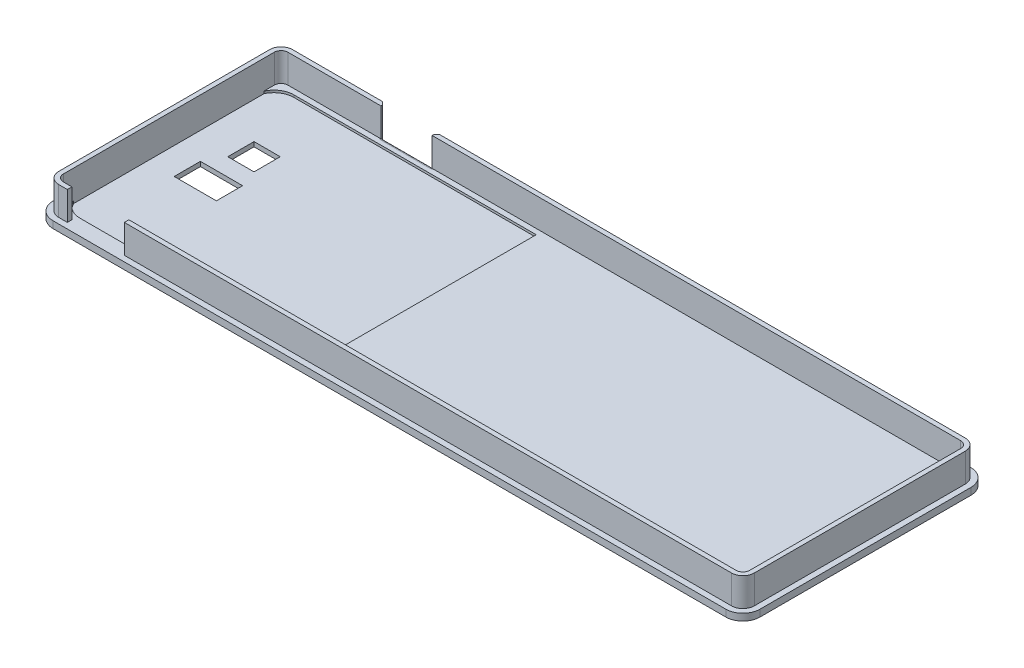
SolidWorks part; units mm, degrees
ref_plane "Спереди" through (0, 0, 0) normal (0, 0, 1) x (1, 0, 0)
ref_plane "Сверху" through (0, 0, 0) normal (0, 1, 0) x (1, 0, 0)
ref_plane "Справа" through (0, 0, 0) normal (1, 0, 0) x (0, 0, -1)
sketch "Эскиз1" plane through (0, 0, 0) normal (0, 1, 0) x (1, 0, 0)
  line L1 (105.9268, 23) -> (-18.0732, 23)
  line L2 (105.9268, 23) -> (105.9268, -20)
  line L3 (105.9268, -20) -> (-18.0732, -20)
  line L4 (-18.0732, 23) -> (-18.0732, -20)
  line L5 (105.9268, 23) -> (-18.0732, -20) construction
  line L6 (105.9268, -20) -> (-18.0732, 23) construction
  line L7 (-16.0732, 16.75) -> (-16.0732, -13.75) construction
  line L9 (103.9268, -18) -> (103.9268, 21) construction
  point P0 (0, 0)
  dimension "D1" = 43
  dimension "D2" = 2
  dimension "D3" = 2
extrude "Бобышка-Вытянуть1" add sketch "Эскиз1" along normal blind 1.2
sketch "Эскиз3" plane through (0, 0, 0) normal (0, -1, 0) x (1, 0, 0)
  line L12 (-11.5732, 2.25) -> (-11.5732, -2.35)
  line L13 (-11.5732, -2.35) -> (-4.1732, -2.35)
  line L14 (-4.1732, -2.35) -> (-4.1732, 2.25)
  line L15 (-4.1732, 2.25) -> (-11.5732, 2.25)
  line L16 (-11.5732, 2.25) -> (-11.5732, -2.35)
  line L17 (-11.5732, -2.35) -> (-4.1732, -2.35)
  line L18 (-4.1732, -2.35) -> (-4.1732, 2.25)
  line L19 (-4.1732, 2.25) -> (-11.5732, 2.25)
  line L24 (-9.8732, -5.45) -> (-9.8732, -10.05)
  line L25 (-9.8732, -10.05) -> (-5.2732, -10.05)
  line L26 (-5.2732, -10.05) -> (-5.2732, -5.45)
  line L27 (-5.2732, -5.45) -> (-9.8732, -5.45)
  line L28 (-9.8732, -5.45) -> (-9.8732, -10.05)
  line L29 (-9.8732, -10.05) -> (-5.2732, -10.05)
  line L30 (-5.2732, -10.05) -> (-5.2732, -5.45)
  line L31 (-5.2732, -5.45) -> (-9.8732, -5.45)
  dimension "D1" = 0.8
  dimension "D2" = 0.8
extrude "Вырез-Вытянуть1" cut sketch "Эскиз3" against normal up to next
sketch "Эскиз4" plane through (0, 1.2, 0) normal (0, 1, 0) x (1, 0, 0)
  line L0 (4.11, 20.25) -> (7.3436, 20.25)
  line L16 (29.4268, 20.25) -> (7.3436, 20.25)
  line L17 (7.3436, 20.25) -> (7.3436, 15.1)
  line L18 (7.3436, 15.1) -> (4.11, 15.1)
  line L19 (4.11, 15.1) -> (4.11, 20.25)
  line L20 (4.11, 20.25) -> (-13.0732, 20.25)
  line L21 (-16.5732, 16.75) -> (-16.5732, -13.75)
  line L22 (-13.0732, -17.25) -> (25.9268, -17.25)
  line L23 (29.4268, -13.75) -> (29.4268, 20.25)
  line L24 (29.4268, 20.25) -> (7.3436, 20.25)
  line L28 (4.11, 20.25) -> (-13.0732, 20.25)
  line L29 (-16.5732, 16.75) -> (-16.5732, -13.75)
  line L30 (-13.0732, -17.25) -> (25.9268, -17.25)
  line L31 (29.4268, -13.75) -> (29.4268, 20.25)
  arc A6 (-13.0732, 20.25) -> (-16.5732, 16.75) centre (-13.0732, 16.75) ccw
  arc A7 (-16.5732, -13.75) -> (-13.0732, -17.25) centre (-13.0732, -13.75) ccw
  arc A8 (25.9268, -17.25) -> (29.4268, -13.75) centre (25.9268, -13.75) ccw
  arc A9 (-13.0732, 20.25) -> (-16.5732, 16.75) centre (-13.0732, 16.75) ccw
  arc A10 (-16.5732, -13.75) -> (-13.0732, -17.25) centre (-13.0732, -13.75) ccw
  arc A11 (25.9268, -17.25) -> (29.4268, -13.75) centre (25.9268, -13.75) ccw
  dimension "D1" = 0.5
extrude "Вырез-Вытянуть2" cut sketch "Эскиз4" against normal blind 0.4
fillet "Скругление1" radius 3 4 edges at (105.9268, 0.6, -23) (105.9268, 0.6, 20) (-18.0732, 0.6, -23) (-18.0732, 0.6, 20)
sketch "Эскиз5" plane through (0, 1.2, 0) normal (0, 1, 0) x (1, 0, 0)
  line L4 (-15.0732, -18.2) -> (102.9268, -18.2)
  line L5 (104.1268, -17) -> (104.1268, 20)
  line L6 (102.9268, 21.2) -> (-15.0732, 21.2)
  line L7 (-16.2732, 20) -> (-16.2732, -17)
  line L8 (104.9268, -17) -> (104.9268, 20)
  line L9 (102.9268, 22) -> (-15.0732, 22)
  line L10 (-17.0732, 20) -> (-17.0732, -17)
  line L11 (-15.0732, -19) -> (102.9268, -19)
  line L12 (104.9268, -17) -> (104.9268, 20)
  line L13 (102.9268, 22) -> (-15.0732, 22)
  line L14 (-17.0732, 20) -> (-17.0732, -17)
  line L15 (-15.0732, -19) -> (102.9268, -19)
  arc A4 (102.9268, -18.2) -> (104.1268, -17) centre (102.9268, -17) ccw
  arc A5 (104.1268, 20) -> (102.9268, 21.2) centre (102.9268, 20) ccw
  arc A6 (-15.0732, 21.2) -> (-16.2732, 20) centre (-15.0732, 20) ccw
  arc A7 (-16.2732, -17) -> (-15.0732, -18.2) centre (-15.0732, -17) ccw
  arc A8 (104.9268, 20) -> (102.9268, 22) centre (102.9268, 20) ccw
  arc A9 (-15.0732, 22) -> (-17.0732, 20) centre (-15.0732, 20) ccw
  arc A10 (-17.0732, -17) -> (-15.0732, -19) centre (-15.0732, -17) ccw
  arc A11 (102.9268, -19) -> (104.9268, -17) centre (102.9268, -17) ccw
  arc A12 (104.9268, 20) -> (102.9268, 22) centre (102.9268, 20) ccw
  arc A13 (-15.0732, 22) -> (-17.0732, 20) centre (-15.0732, 20) ccw
  arc A14 (-17.0732, -17) -> (-15.0732, -19) centre (-15.0732, -17) ccw
  arc A15 (102.9268, -19) -> (104.9268, -17) centre (102.9268, -17) ccw
  point P16 (0, 0)
  arc M13 (-13.0732, -17.25) -> (-16.5732, -13.75) centre (-13.0732, -13.75) cw
  line M14 (-16.5732, -13.75) -> (-16.5732, 16.75)
  arc M15 (-16.5732, 16.75) -> (-13.0732, 20.25) centre (-13.0732, 16.75) cw
  dimension "D3" = 0.8
  dimension "D1" = 1
  dimension "D2" = 0.8
extrude "Бобышка-Вытянуть5" add sketch "Эскиз5" along normal blind 5 contours L15 A15 L12 A12 L13 A13 L14 A14 A7 L7 A6 L6 A5 L5 A4 L4 M13 M14 M15
ref_plane "Плоскость2" through (0, 0, 15.1677) normal (0, 0, -1) x (-1, 0, 0)
sketch "Эскиз7" plane through (0, 0, 15.1677) normal (0, 0, -1) x (-1, 0, 0)
  line L0 (17.0732, 6.2) -> (17.0732, 1.2) construction
  line L1 (16.2732, 6.2) -> (17.0732, 6.2)
  line L2 (16.2732, 6.2) -> (16.2732, 0.8)
  line L3 (16.2732, 0.8) -> (17.0732, 0.8)
  line L4 (17.0732, 6.2) -> (17.0732, 0.8)
  line L5 (16.2732, 6.2) -> (16.2732, 1.2) construction
  line L6 (16.2732, 6.2) -> (15.0732, 6.2) construction
  line L7 (4.1732, 0.8) -> (11.5732, 0.8) construction
extrude "Бобышка-Вытянуть6" add sketch "Эскиз7" along normal up to vertex
sketch "Эскиз8" plane through (0, 6.2, 0) normal (0, 1, 0) x (1, 0, 0)
  line L0 (10.2268, 21.2) -> (10.2268, 22)
  line L1 (102.9268, 21.2) -> (-15.0732, 21.2) construction
  line L2 (102.9268, 22) -> (-15.0732, 22) construction
  line L3 (1.2268, 21.2) -> (1.2268, 22)
  line L4 (5.7268, 21.2) -> (5.7268, 22) construction
  line L5 (-17.0732, 20) -> (-17.0732, -17) construction
  point P10 (10.2268, 21.6)
  point P11 (1.2268, 21.6)
  line M8 (102.9268, 22) -> (-15.0732, 22)
  line M12 (-15.0732, 21.2) -> (102.9268, 21.2)
  dimension "D1" = 22.8
  dimension "D2" = 9
extrude "Вырез-Вытянуть3" cut sketch "Эскиз8" against normal blind 5 contours L4 L0 M12 M8 | L4 L3 M12 M8
chamfer "Фаска2" distance 0.5 angle 45 2 edges at (1.2268, 3.7, -22) (10.2268, 3.7, -22)
sketch "Эскиз9" plane through (0, 1.2, 0) normal (0, 1, 0) x (1, 0, 0)
  line L0 (10.2268, 21.5) -> (11.7268, 23)
  line L1 (102.9268, 23) -> (-15.0732, 23) construction
  line L2 (1.2268, 21.5) -> (-0.2732, 23)
  line L3 (10.2268, 21.5) -> (1.2268, 21.5)
  line M6 (0.7268, 22) -> (1.2268, 21.5)
  line M25 (10.2268, 21.5) -> (10.7268, 22)
  line M32 (102.9268, 23) -> (-15.0732, 23)
extrude "Вырез-Вытянуть5" cut sketch "Эскиз9" against normal through all and the other way through all contours L3 L0 L2 M25 M32 M6
fillet "Скругление2" radius 3 2 edges at (-0.2732, 0.6, -23) (11.7268, 0.6, -23)
fillet "Скругление3" radius 1 2 edges at (1.2268, 0.6, -21.5) (10.2268, 0.6, -21.5)
fillet "Скругление4" radius 0.5 7 edges at (10.2268, 1.2, -21.35) (1.2268, 1.2, -21.35) (5.7268, 1.2, -21.5) (1.0804, 1.2, -21.6464) (10.3733, 1.2, -21.6464) (1.2584, 1.2, -21.5761) (10.1953, 1.2, -21.5761)
sketch "Эскиз10" plane through (0, 6.2, 0) normal (0, 1, 0) x (1, 0, 0)
  line L0 (-13.5732, -18.2) -> (-13.5732, -19)
  line L1 (-15.0732, -18.2) -> (102.9268, -18.2) construction
  line L2 (-15.0732, -19) -> (102.9268, -19) construction
  line L3 (-18.0732, 20) -> (-18.0732, -17) construction
  line L4 (-3.5732, -18.2) -> (-3.5732, -19)
  point P10 (-3.5732, -18.6)
  line M8 (-15.0732, -19) -> (102.9268, -19)
  line M19 (102.9268, -18.2) -> (-15.0732, -18.2)
  dimension "D1" = 4.5
  dimension "D2" = 10
extrude "Вырез-Вытянуть6" cut sketch "Эскиз10" against normal up to vertex (5 mm away) contours L4 L0 M19 M8
